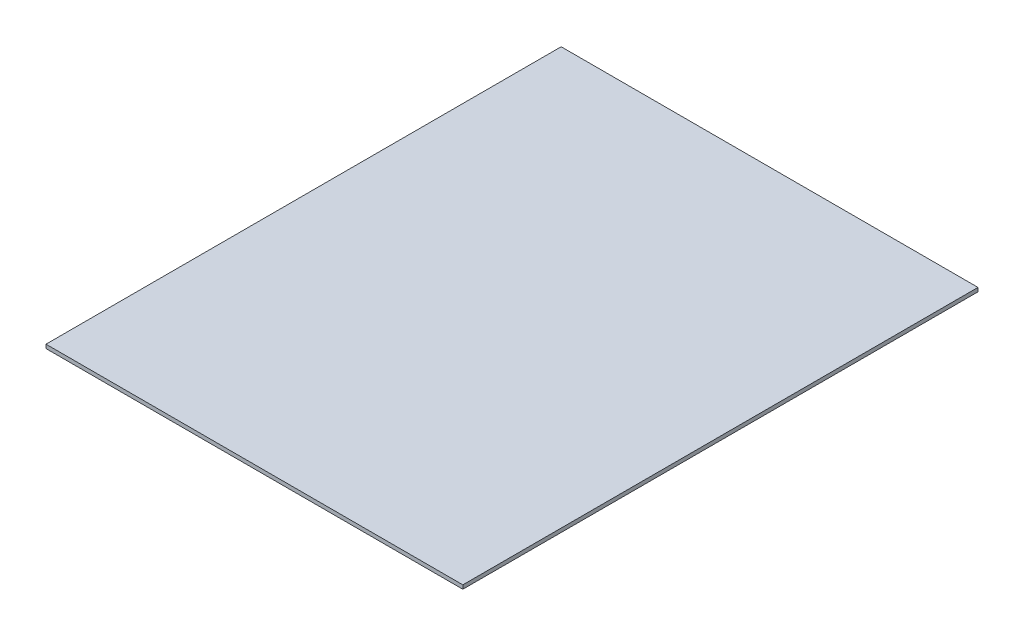
SolidWorks part; units mm, degrees
ref_plane "Front Plane" through (0, 0, 0) normal (0, 0, 1) x (1, 0, 0)
ref_plane "Top Plane" through (0, 0, 0) normal (0, 1, 0) x (1, 0, 0)
ref_plane "Right Plane" through (0, 0, 0) normal (1, 0, 0) x (0, 0, -1)
sketch "Sketch1" plane through (0, 0, 0) normal (0, 1, 0) x (1, 0, 0)
  line L1 (-163, 201.45) -> (163, 201.45)
  line L2 (-163, 201.45) -> (-163, -201.45)
  line L3 (-163, -201.45) -> (163, -201.45)
  line L4 (163, 201.45) -> (163, -201.45)
  line L5 (-163, 201.45) -> (163, -201.45) construction
  line L6 (-163, -201.45) -> (163, 201.45) construction
  point P0 (0, 0)
  dimension "D1" = 326
  dimension "D2" = 402.9
extrude "Boss-Extrude1" add sketch "Sketch1" along normal blind 3
